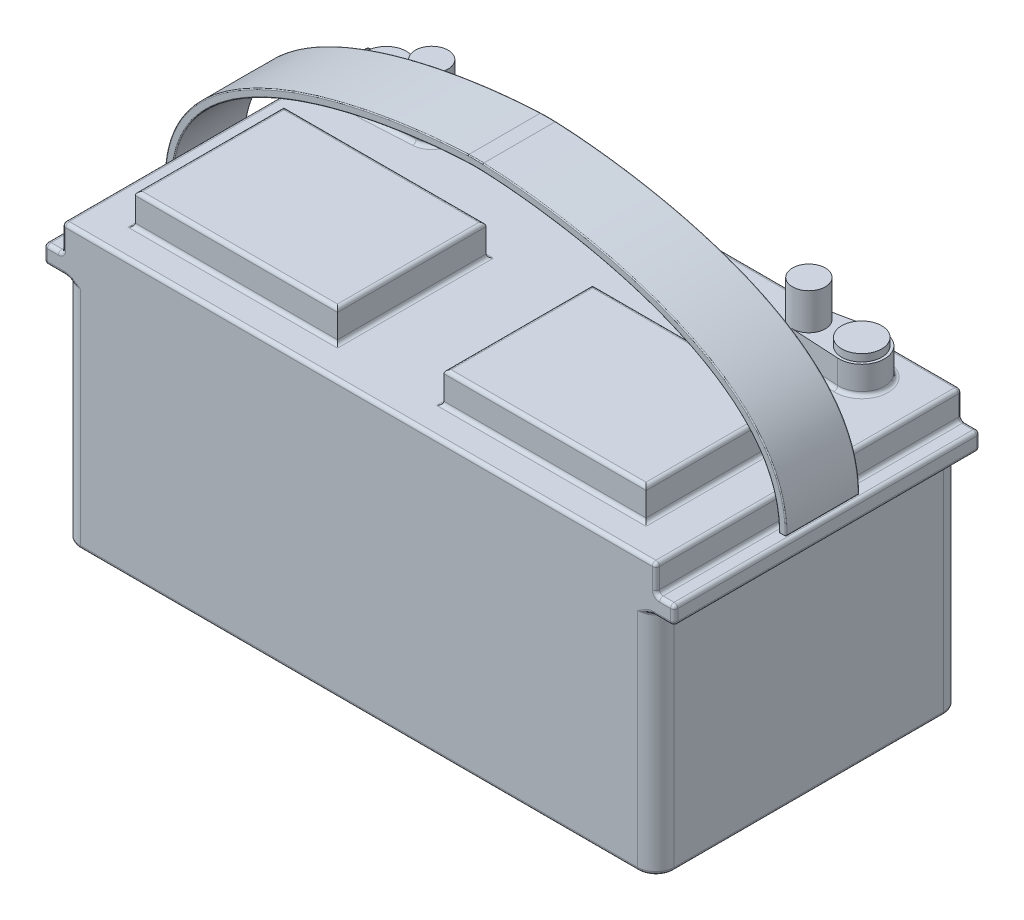
SolidWorks part; units mm, degrees
ref_plane "Front Plane" through (0, 0, 0) normal (0, 0, 1) x (1, 0, 0)
ref_plane "Top Plane" through (0, 0, 0) normal (0, 1, 0) x (1, 0, 0)
ref_plane "Right Plane" through (0, 0, 0) normal (1, 0, 0) x (0, 0, -1)
sketch "Sketch1" plane through (0, 0, 0) normal (0, 1, 0) x (1, 0, 0)
  line L0 (0, -55) -> (0, 55) construction
  line L1 (-163, 84) -> (163, 84)
  line L2 (-163, 84) -> (-163, -84)
  line L3 (-163, -84) -> (163, -84)
  line L4 (163, 84) -> (163, -84)
  line L5 (-55, 0) -> (55, 0) construction
  dimension "D1" = 326
  dimension "D2" = 168
  dimension "D3" = 163
  dimension "D4" = 84
extrude "Boss-Extrude1" add sketch "Sketch1" along normal blind 168
sketch "Sketch2" plane through (0, 168, 0) normal (0, 1, 0) x (1, 0, 0)
  line L0 (163, -84) -> (163, 84) construction
  line L1 (29.2, 15) -> (140.2, 15)
  line L2 (29.2, 15) -> (29.2, -66.6)
  line L3 (29.2, -66.6) -> (140.2, -66.6)
  line L4 (140.2, 15) -> (140.2, -66.6)
  line L5 (163, 84) -> (-163, 84) construction
  line L6 (0, 84) -> (0, -84) construction
  line L7 (-163, -84) -> (163, -84) construction
  line L8 (-140.2, 15) -> (-140.2, -66.6)
  line L9 (-29.2, -66.6) -> (-140.2, -66.6)
  line L10 (-29.2, 15) -> (-29.2, -66.6)
  line L11 (-29.2, 15) -> (-140.2, 15)
  line L13 (-163, 84) -> (163, 84)
  line L14 (-163, 84) -> (-163, -84)
  line L15 (-163, -84) -> (163, -84)
  line L16 (163, 84) -> (163, -84)
  dimension "D1" = 22.8
  dimension "D2" = 69
  dimension "D3" = 111
  dimension "D4" = 81.6
extrude "Cut-Extrude1" cut sketch "Sketch2" against normal blind 17
sketch "Sketch3" plane through (163, 0, 0) normal (1, 0, 0) x (0, 0, -1)
  line L6 (-84, 151) -> (84, 151) construction
  line L7 (0, 151) -> (0, 0) construction
  line L24 (-84, 0) -> (84, 0) construction
sketch "Sketch4" plane through (163, 0, 0) normal (1, 0, 0) x (0, 0, -1)
  line L0 (-84, 151) -> (-84, 0) construction
  line L1 (-84, 126) -> (84, 126)
  line L2 (-84, 126) -> (-84, 136)
  line L3 (-84, 136) -> (84, 136)
  line L4 (84, 126) -> (84, 136)
  line L5 (84, 151) -> (84, 0) construction
  line L7 (-84, 151) -> (84, 151) construction
  dimension "D1" = 15
  dimension "D2" = 10
extrude "Boss-Extrude2" add sketch "Sketch4" along normal blind 10
mirror "Mirror1" about plane through (0, 0, 0) normal (1, 0, 0) of "Boss-Extrude2"
sketch "Sketch5" plane through (0, 0, 0) normal (0, 0, 1) x (1, 0, 0)
  line L0 (-173, 136) -> (-163, 136) construction
  line L2 (0, -92.4) -> (0, 92.4) construction
  line L4 (-170.531, 136) -> (-166.531, 136.0075)
  line L5 (166.531, 136.0075) -> (170.531, 136)
  spline S0 degree 3 poles (-170.531, 136) (-170.6754, 213.3494) (-42.8275, 229.2844) (0, 230.2964) knots 0 0 0 0 1 1 1 1
  spline S1 degree 1 poles (-166.531, 136.0075) (0.0945, 226.2975) knots 0 0 1 1 construction
  spline S2 degree 3 poles (-166.531, 136.0075) (-166.5331, 137.1318) (-166.4785, 139.4019) (-166.1407, 143.7634) (-165.3037, 149.0107) (-163.6744, 154.9652) (-160.7138, 162.4923) (-155.61, 171.1741) (-147.4644, 180.5357) (-137.5449, 188.885) (-122.3326, 198.7056) (-104.7531, 206.6186) (-86.0803, 212.8088) (-71.8501, 216.6488) (-57.7131, 219.7462) (-43.9878, 222.1643) (-33.1579, 223.6673) (-25.0176, 224.5955) (-19.2141, 225.1628) (-13.7519, 225.6096) (-9.519, 225.8886) (-6.3425, 226.0601) (-4.075, 226.1637) (-1.9512, 226.2424) (-0.6286, 226.2801) (0.0316, 226.296) (0.0702, 226.297) (0.0945, 226.2975) knots 0 0 0 0 0.015625 0.03125 0.0625 0.09375 0.125 0.1875 0.25 0.3125 0.375 0.5 0.5625 0.625 0.6875 0.75 0.8125 0.84375 0.875 0.90625 0.9375 0.953125 0.96875 0.984375 0.999064 0.999439 1 1 1 1 only from (-166.531, 136.0075) to (0, 226.2953)
  spline S3 degree 3 poles (166.531, 136.0075) (166.5331, 137.1318) (166.4785, 139.4019) (166.1407, 143.7634) (165.3037, 149.0107) (163.6744, 154.9652) (160.7138, 162.4923) (155.61, 171.1741) (147.4644, 180.5357) (137.5449, 188.885) (122.3326, 198.7056) (104.7531, 206.6186) (86.0803, 212.8088) (71.8501, 216.6488) (57.7131, 219.7462) (43.9878, 222.1643) (33.1579, 223.6673) (25.0176, 224.5955) (19.2141, 225.1628) (13.7519, 225.6096) (9.519, 225.8886) (6.3425, 226.0601) (4.075, 226.1637) (1.9416, 226.2428) (0.6448, 226.2798) (0, 226.2953) knots 0 0 0 0 0.015625 0.03125 0.0625 0.09375 0.125 0.1875 0.25 0.3125 0.375 0.5 0.5625 0.625 0.6875 0.75 0.8125 0.84375 0.875 0.90625 0.9375 0.953125 0.96875 0.984375 0.999273 0.999273 0.999273 0.999273
  spline S4 degree 3 poles (170.531, 136) (170.6754, 213.3494) (42.8275, 229.2844) (0, 230.2964) knots 0 0 0 0 1 1 1 1
  dimension "D1" = 4
extrude "Boss-Extrude3" add sketch "Sketch5" along normal blind 20 and the other way blind 20 separate body
fillet "Fillet1" radius 100 2 edges at (0, 226.2953, 0) (0, 230.2964, 0)
sketch "Sketch6" plane through (0, 151, 0) normal (0, 1, 0) x (1, 0, 0)
  line L0 (-127.9773, 73.7079) -> (-101.7116, 68.2565)
  line L1 (-129.8323, 48.9875) -> (-103.0473, 50.4579)
  line L2 (0, -92.4) -> (0, 92.4) construction
  line L3 (129.8323, 48.9875) -> (103.0473, 50.4579)
  line L4 (127.9773, 73.7079) -> (101.7116, 68.2565)
  arc A0 (-127.9773, 73.7079) -> (-129.8323, 48.9875) centre (-130.5175, 61.4687) ccw
  arc A1 (-103.0473, 50.4579) -> (-101.7116, 68.2565) centre (-103.5406, 59.4443) ccw
  arc A2 (103.0473, 50.4579) -> (101.7116, 68.2565) centre (103.5406, 59.4443) cw
  arc A3 (127.9773, 73.7079) -> (129.8323, 48.9875) centre (130.5175, 61.4687) cw
  dimension "D1" = 25
  dimension "D2" = 18
extrude "Boss-Extrude4" add sketch "Sketch6" along normal blind 15
sketch "Sketch7" plane through (0, 166, 0) normal (0, 1, 0) x (1, 0, 0)
  circle A1 centre (130.5175, 61.4687) radius 11
  arc A2 (129.8323, 48.9875) -> (127.9773, 73.7079) centre (130.5175, 61.4687) ccw construction
  dimension "D1" = 22
extrude "Boss-Extrude5" add sketch "Sketch7" along normal blind 4
sketch "Sketch8" plane through (0, 166, 0) normal (0, 1, 0) x (1, 0, 0)
  circle A0 centre (103.5406, 59.4443) radius 9
  arc A1 (101.7116, 68.2565) -> (103.0473, 50.4579) centre (103.5406, 59.4443) ccw construction
extrude "Boss-Extrude6" add sketch "Sketch8" along normal blind 20
fillet "Fillet2" radius 10 4 edges at (-163, 63, -84) (163, 63, -84) (163, 63, 84) (-163, 63, 84)
fillet "Fillet3" radius 2 64 edges at (160.0711, 126, 81.0711) (160.0711, 126, -81.0711) (-160.0711, 0, 81.0711) (-160.0711, 0, -81.0711) (160.0711, 0, -81.0711) (160.0711, 0, 81.0711) (-160.0711, 126, -81.0711) (-160.0711, 126, 81.0711) (-173, 126, 0) (-173, 136, 0) (-163, 136, 0) (-163, 0, 0) (-163, 126, 0) (163, 126, 0) (163, 0, 0) (163, 126, -84) (-163, 143.5, -84) (-168, 136, -84) (-173, 131, -84) (-163, 126, -84) (0, 0, -84) (-163, 126, 84) (-173, 131, 84) (-168, 136, 84) (-163, 143.5, 84) (163, 126, 84) (0, 0, 84) (173, 131, -84) (173, 126, 0) (173, 131, 84) (168, 136, -84) (173, 136, 0) (168, 136, 84) (163, 143.5, 84) (163, 143.5, -84) (163, 136, 0) (140.2, 168, 25.8) (84.7, 168, 66.6) (29.2, 168, 25.8) (84.7, 168, -15) (-84.7, 168, 66.6) (-140.2, 168, 25.8) (-84.7, 168, -15) (-29.2, 168, 25.8) (142.9824, 151, -62.4041) (114.8444, 151, -70.9822) (94.5658, 151, -58.7708) (116.4398, 151, -49.7227) (-142.9824, 151, -62.4041) (-116.4398, 151, -49.7227) (-94.5658, 151, -58.7708) (-114.8444, 151, -70.9822) (0, 151, -84) (163, 151, 0) (0, 151, 84) (-163, 151, 0) (29.2, 151, 25.8) (84.7, 151, 66.6) (140.2, 151, 25.8) (84.7, 151, -15) (-84.7, 151, -15) (-140.2, 151, 25.8) (-84.7, 151, 66.6) (-29.2, 151, 25.8)
fillet "Fillet4" radius 0.5 16 edges at (166.531, 136.0075, 0) (0, 226.2436, 20) (0, 226.2436, -20) (-166.531, 136.0075, 0) (0, 230.247, 20) (0, 230.247, -20) (170.531, 136, 0) (-170.531, 136, 0)
mirror "Mirror2" about plane through (0, 0, 0) normal (1, 0, 0) of "Boss-Extrude6", "Boss-Extrude5"
